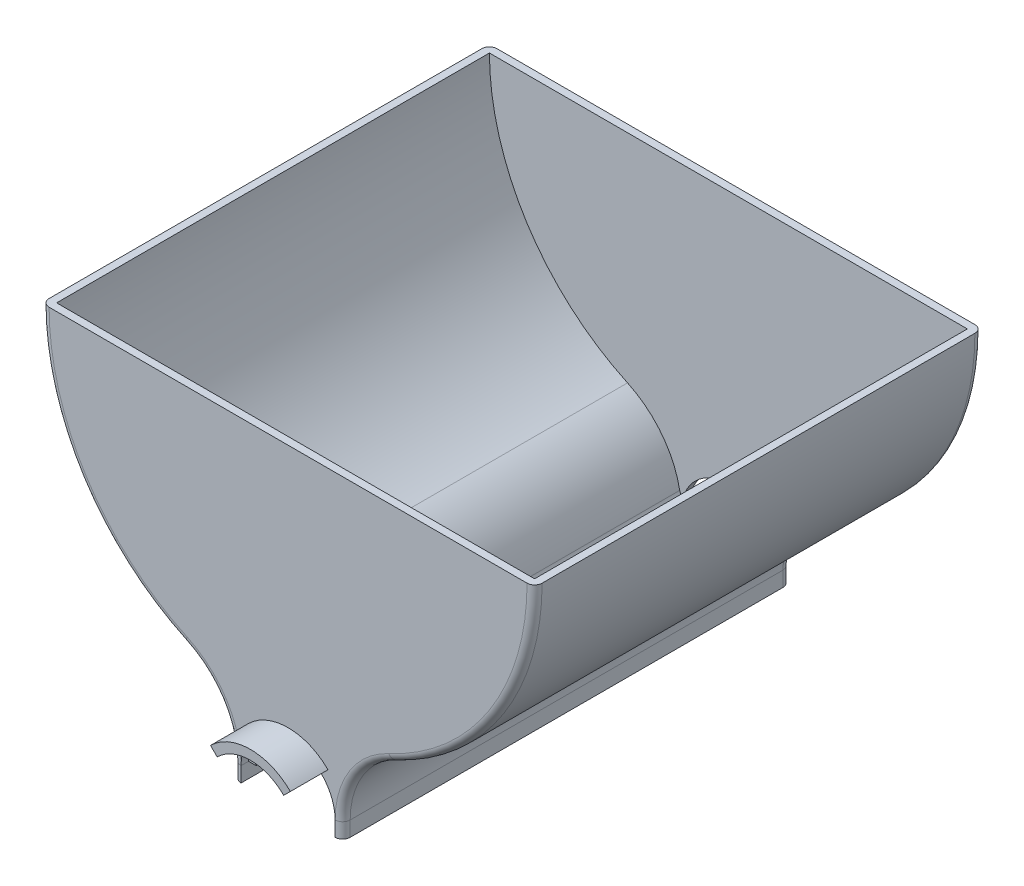
SolidWorks part; units mm, degrees
note: The reader was unsure of these and kept them because the rebuilt part matched: shared geometry of "Schizzo2<4>".
material "Gomma"
ref_plane "Piano frontale" through (0, 0, 0) normal (0, 0, 1) x (1, 0, 0)
ref_plane "Piano superiore" through (0, 0, 0) normal (0, 1, 0) x (1, 0, 0)
ref_plane "Piano destro" through (0, 0, 0) normal (1, 0, 0) x (0, 0, -1)
sketch "Schizzo1" plane through (0, 0, 0) normal (0, 0, 1) x (1, 0, 0)
  line L0 (-65.5, 80) -> (-63.5, 80)
  line L1 (63.5, 80) -> (65.5, 80)
  line L2 (0, -0.9157) -> (0, 1.3608) construction
  line L4 (-14.5, 0) -> (-14.5, -4)
  line L5 (-14.5, -4) -> (-12.5, -4)
  line L6 (-12.5, -4) -> (-12.5, 0)
  line L7 (-10.5, 0) -> (-12.5, 0)
  line L8 (-10.5, 0) -> (-10.5, 3)
  line L9 (-10.5, 3) -> (-10.9715, 3)
  line L10 (10.5, 3) -> (10.9715, 3)
  line L11 (10.5, 0) -> (10.5, 3)
  line L12 (10.5, 0) -> (12.5, 0)
  line L13 (12.5, -4) -> (12.5, 0)
  line L14 (14.5, -4) -> (12.5, -4)
  line L15 (14.5, 0) -> (14.5, -4)
  arc A0 (-12.5, 0) -> (12.5, 0) centre (0, 0) ccw construction
  arc A1 (-14.5, 0) -> (14.5, 0) centre (0, 0) ccw construction
  arc A2 (-65.5, 80) -> (-27.6452, 20.6199) centre (0, 80) ccw
  arc A3 (-63.5, 80) -> (-26.8011, 22.4331) centre (0, 80) ccw
  arc A4 (-14.5, 0) -> (-27.6452, 20.6199) centre (-37.2451, 0) ccw
  arc A5 (27.6452, 20.6199) -> (14.5, 0) centre (37.2451, 0) ccw
  arc A6 (-12.9363, 4.6261) -> (-26.8011, 22.4331) centre (-37.2451, 0) ccw
  arc A7 (26.8011, 22.4331) -> (12.9363, 4.6261) centre (37.2451, 0) ccw
  arc A8 (27.6452, 20.6199) -> (65.5, 80) centre (0, 80) ccw
  arc A9 (26.8011, 22.4331) -> (63.5, 80) centre (0, 80) ccw
  arc A10 (10.9715, 3) -> (12.9363, 4.6261) centre (10.9715, 5) ccw
  arc A11 (-10.9715, 3) -> (-12.9363, 4.6261) centre (-10.9715, 5) cw
  point P35 (12.6825, 3)
  point P38 (-12.6825, 3)
  dimension "D1" = 25
  dimension "D2" = 2
  dimension "D3" = 2
  dimension "D4" = 2
  dimension "D7" = 2
  dimension "D5" = 2
  dimension "D6" = 80
  dimension "D8" = 2
  dimension "D9" = 3
  dimension "D10" = 4
extrude "Estrusione-Estrusione1" add sketch "Schizzo1" along normal blind 119
sketch "Schizzo2" plane through (0, 0, 119) normal (0, 0, 1) x (1, 0, 0)
  line L0 (65.5, 80) -> (-65.5, 80)
  line L1 (14.5, -4) -> (-14.5, -4)
  line L7 (65.5, 80) -> (63.5, 80)
  line L8 (10.9715, 3) -> (10.5, 3)
  line L9 (10.5, 3) -> (10.5, 0)
  line L10 (10.5, 0) -> (12.5, 0)
  line L11 (12.5, 0) -> (12.5, -4)
  line L12 (12.5, -4) -> (14.5, -4)
  line L13 (14.5, -4) -> (14.5, 0)
  line L20 (14.5, -4) -> (14.5, 0)
  line L21 (-10.5, 0) -> (-10.5, 3)
  line L22 (-10.5, 3) -> (-10.9715, 3)
  line L23 (-63.5, 80) -> (-65.5, 80)
  line L24 (-14.5, 0) -> (-14.5, -4)
  line L25 (-14.5, -4) -> (-12.5, -4)
  line L26 (-12.5, -4) -> (-12.5, 0)
  line L27 (-12.5, 0) -> (-10.5, 0)
  line L31 (-14.5, 0) -> (-14.5, -4)
  arc A5 (27.6452, 20.6199) -> (14.5, 0) centre (37.2451, 0) ccw
  arc A6 (27.6452, 20.6199) -> (65.5, 80) centre (0, 80) ccw
  arc A7 (26.8011, 22.4331) -> (63.5, 80) centre (0, 80) ccw
  arc A8 (26.8011, 22.4331) -> (12.9363, 4.6261) centre (37.2451, 0) ccw
  arc A9 (10.9715, 3) -> (12.9363, 4.6261) centre (10.9715, 5) ccw
  arc A10 (27.6452, 20.6199) -> (14.5, 0) centre (37.2451, 0) ccw
  arc A11 (27.6452, 20.6199) -> (65.5, 80) centre (0, 80) ccw
  arc A15 (-12.9363, 4.6261) -> (-10.9715, 3) centre (-10.9715, 5) ccw
  arc A16 (-12.9363, 4.6261) -> (-26.8011, 22.4331) centre (-37.2451, 0) ccw
  arc A17 (-63.5, 80) -> (-26.8011, 22.4331) centre (0, 80) ccw
  arc A18 (-65.5, 80) -> (-27.6452, 20.6199) centre (0, 80) ccw
  arc A19 (-14.5, 0) -> (-27.6452, 20.6199) centre (-37.2451, 0) ccw
  arc A22 (-63.5, 80) -> (-26.8011, 22.4331) centre (0, 80) ccw
  arc A23 (-65.5, 80) -> (-27.6452, 20.6199) centre (0, 80) ccw
  arc A24 (-14.5, 0) -> (-27.6452, 20.6199) centre (-37.2451, 0) ccw
  dimension "D1" = 0
  dimension "D2" = 0
extrude "Estrusione-Estrusione2" add sketch "Schizzo2" against normal blind 2 contours L0 A23 A24 L31 L1 L20 A10 A11
extrude "Estrusione-Estrusione4" add sketch "Schizzo2<4>" along normal blind 2 from surface at -119 starting at plane "Piano frontale"
sketch "Schizzo2<4>" plane through (0, 0, 119) normal (0, 0, 1) x (1, 0, 0) same geometry as "Schizzo2"
fillet "Raccordo1" radius 2 12 edges at (-14.5, -2, 0) (-14.5, -2, 119) (-18.0658, 12.2268, 0) (-18.0658, 12.2268, 119) (14.5, -2, 119) (14.5, -2, 0) (18.0658, 12.2268, 119) (18.0658, 12.2268, 0) (-55.2314, 44.79, 0) (-55.2314, 44.79, 119) (55.2314, 44.79, 119) (55.2314, 44.79, 0)
sketch "Schizzo3" plane through (0, 0, 119) normal (0, 0, 1) x (1, 0, 0)
  line L0 (-12.5, 0) -> (-12.5, -4)
  line L1 (-12.5, -4) -> (12.5, -4)
  line L2 (12.5, -4) -> (12.5, 0)
  line L3 (-12.5, 0) -> (-10.5, 0) construction
  line L4 (-10.5, 0) -> (-10.5, 3) construction
  line L5 (-10.5, 3) -> (-10.9715, 3) construction
  line L6 (10.9715, 3) -> (10.5, 3) construction
  line L7 (10.5, 3) -> (10.5, 0) construction
  line L8 (10.5, 0) -> (12.5, 0) construction
  line L9 (-12.5, 0) -> (-10.5, 0)
  line L10 (-10.5, 0) -> (-10.5, 3)
  line L11 (-10.5, 3) -> (-10.9715, 3)
  line L12 (10.9715, 3) -> (10.5, 3)
  line L13 (10.5, 3) -> (10.5, 0)
  line L14 (10.5, 0) -> (12.5, 0)
  arc A0 (12.0519, 3.3169) -> (-12.0519, 3.3169) centre (0, 0) ccw
  arc A1 (-12.9363, 4.6261) -> (-10.9715, 3) centre (-10.9715, 5) ccw construction
  arc A2 (10.9715, 3) -> (12.9363, 4.6261) centre (10.9715, 5) ccw construction
  arc A3 (-12.0519, 3.3169) -> (-10.9715, 3) centre (-10.9715, 5) ccw
  arc A4 (10.9715, 3) -> (12.0519, 3.3169) centre (10.9715, 5) ccw
extrude "Taglio-Estrusione1" cut sketch "Schizzo3" against normal through all
sketch "Schizzo5" plane through (0, 0, 119) normal (0, 0, 1) x (1, 0, 0)
  line L0 (-12.5, 0) -> (12.5, 0)
  arc A0 (12.5, 0) -> (-12.5, 0) centre (0, 0) ccw
  arc A1 (12.0519, 3.3169) -> (-12.0519, 3.3169) centre (0, 0) ccw construction
extrude "Taglio-Estrusione2" cut sketch "Schizzo5" against normal up to vertex (2 mm away) up to point (12.0519, 3.3169, 117)
sketch "Schizzo7" plane through (0, 0, 0) normal (0, 0, -1) x (-1, 0, 0)
  line L0 (12.5, 0) -> (-12.5, 0) construction
  line L1 (12.5, 0) -> (-12.5, 0)
  arc A0 (12.5, 0) -> (-12.5, 0) centre (0, 0) ccw construction
  arc A1 (12.5, 0) -> (-12.5, 0) centre (0, 0) ccw
extrude "Taglio-Estrusione3" cut sketch "Schizzo7" against normal up to vertex (2 mm away) up to point (-12.0519, 3.3169, 2)
sketch "Schizzo8" plane through (0, 0, 0) normal (0, 0, -1) x (-1, 0, 0)
  line L0 (-8.8388, 8.8388) -> (-10.6066, 10.6066)
  line L1 (0, -4.588) -> (0, 8.715) construction
  line L2 (8.8388, 8.8388) -> (10.6066, 10.6066)
  arc A0 (8.8388, 8.8388) -> (-8.8388, 8.8388) centre (0, 0) ccw
  arc A1 (10.6066, 10.6066) -> (-10.6066, 10.6066) centre (0, 0) ccw
  arc A2 (12.5, 0) -> (-12.5, 0) centre (0, 0) ccw construction
  dimension "D1" = 30
  dimension "D2" = 90
extrude "Estrusione-Estrusione5" add sketch "Schizzo8" along normal blind 10
sketch "Schizzo10" plane through (0, 0, 119) normal (0, 0, 1) x (1, 0, 0)
  line L0 (8.8388, 8.8388) -> (10.6066, 10.6066) construction
  line L1 (-8.8388, 8.8388) -> (-10.6066, 10.6066) construction
  line L2 (8.8388, 8.8388) -> (10.6066, 10.6066)
  line L3 (-8.8388, 8.8388) -> (-10.6066, 10.6066)
  arc A0 (10.6066, 10.6066) -> (-10.6066, 10.6066) centre (0, 0) ccw construction
  arc A1 (8.8388, 8.8388) -> (-8.8388, 8.8388) centre (0, 0) ccw construction
  arc A2 (10.6066, 10.6066) -> (-10.6066, 10.6066) centre (0, 0) ccw
  arc A3 (8.8388, 8.8388) -> (-8.8388, 8.8388) centre (0, 0) ccw
extrude "Estrusione-Estrusione6" add sketch "Schizzo10" along normal blind 10
